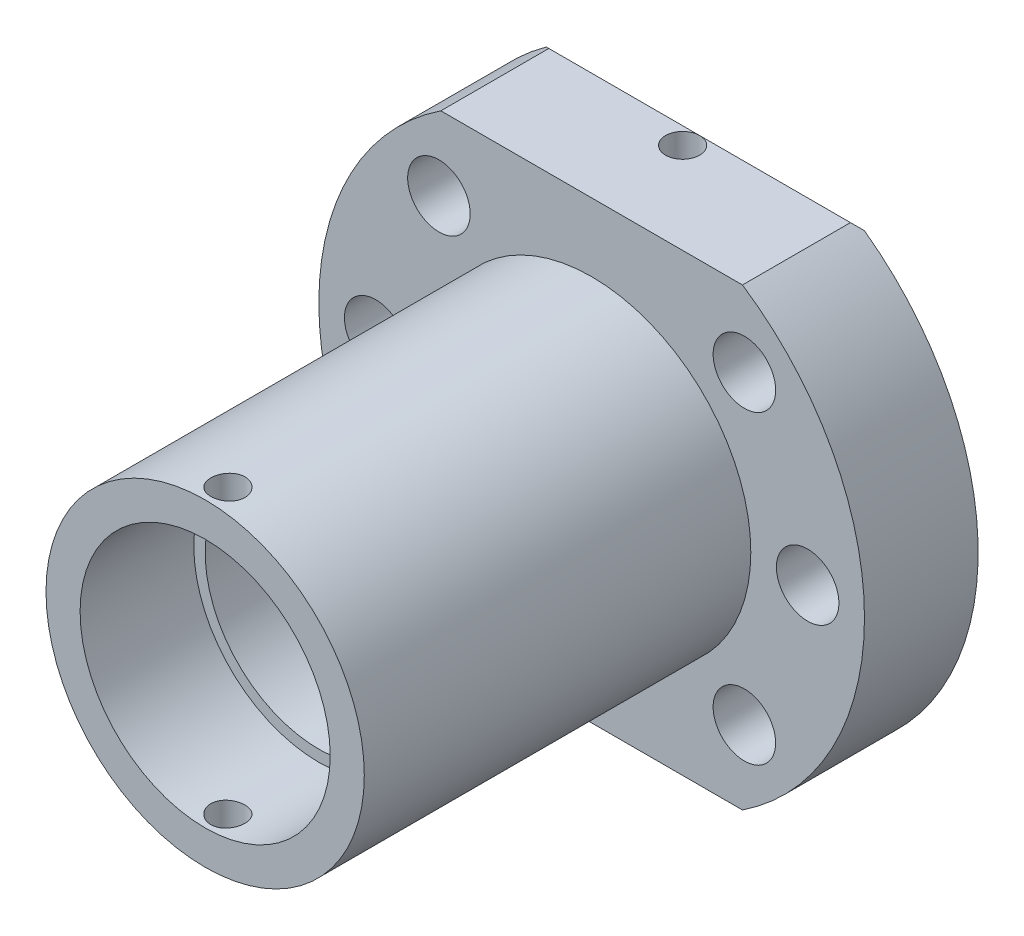
SolidWorks part; units mm, degrees
note: The reader was unsure of these and kept them because the rebuilt part matched: shared geometry of "Sketch1<3>".
ref_plane "Front Plane" through (0, 0, 0) normal (0, 0, 1) x (1, 0, 0)
ref_plane "Top Plane" through (0, 0, 0) normal (0, 1, 0) x (1, 0, 0)
ref_plane "Right Plane" through (0, 0, 0) normal (1, 0, 0) x (0, 0, -1)
sketch "Sketch1" plane through (0, 0, 0) normal (0, 0, 1) x (1, 0, 0)
  line L0 (0, 29.6092) -> (0, -29.6092) construction
  line L1 (-13.2665, 20) -> (13.2665, 20)
  line L2 (-28.8526, 0) -> (28.8526, 0) construction
  line L3 (-13.2665, -20) -> (13.2665, -20)
  circle A0 centre (0, 0) radius 11
  circle A1 centre (0, 0) radius 14
  circle A2 centre (0, 0) radius 19 construction
  arc A3 (-13.2665, 20) -> (-13.2665, -20) centre (0, 0) ccw
  circle A4 centre (19, 0) radius 2.75
  circle A5 centre (13.435, -13.435) radius 2.75
  circle A7 centre (0, -19) radius 2.75 [skipped]
  circle A8 centre (13.435, 13.435) radius 2.75
  circle A9 centre (-13.435, -13.435) radius 2.75
  circle A10 centre (-19, 0) radius 2.75
  circle A11 centre (-13.435, 13.435) radius 2.75
  arc A12 (13.2665, -20) -> (13.2665, 20) centre (0, 0) ccw
  circle A13 centre (0, 0) radius 10
  point P10 (0, 0)
  point P15 (0, 0)
  point P25 (0, 0)
  dimension "D1" = 38
  dimension "D2" = 48
  dimension "D4" = 22
  dimension "D5" = 28
  dimension "D6" = 5.5
  dimension "D9" = 20
  dimension "D3" = 40
  dimension "D8" = 26.8701
  dimension "D7" = 3
extrude "Boss-Extrude1" add sketch "Sketch1" against normal blind 10 contours L3 A12 L1 A3 A10 A8 A5 A4 A1 A9 A11
extrude "Boss-Extrude2" add sketch "Sketch1<3>" along normal blind 24 separate body contours A1 A0 | A0 A13
sketch "Sketch1<3>" plane through (0, 0, 0) normal (0, 0, 1) x (1, 0, 0) same geometry as "Sketch1"
sketch "Sketch3" plane through (0, 0, 24) normal (0, 0, 1) x (1, 0, 0)
  circle A0 centre (0, 0) radius 14
  circle A1 centre (0, 0) radius 11
  point P5 (0, 0)
  dimension "D1" = 28
  dimension "D2" = 22
extrude "Boss-Extrude3" add sketch "Sketch3" along normal blind 10
chamfer "Chamfer1" distance 0.5 angle 45 2 edges at (0, -20, -10) (0, 20, -10)
sketch "Sketch4" plane through (0, 20, 0) normal (0, 1, 0) x (1, 0, 0)
  line L0 (-13.9911, 10) -> (13.9911, 10) construction
  line L1 (13.2665, 9.5) -> (-13.2665, 9.5) construction
  circle A0 centre (0, 8) radius 1.5
  circle A1 centre (0, -32) radius 1.5
  point P4 (0, 0)
  point P6 (0, 0)
  point P7 (0, 7.3571)
  point P10 (0, 0)
  dimension "D1" = 40
  dimension "D2" = 2
extrude "Cut-Extrude1" cut sketch "Sketch4" against normal through all
ref_plane "Plane1" through (0, 0, -5) normal (0, 0, 1) x (1, 0, 0)
sketch "Sketch7" plane through (0, 0, -5) normal (0, 0, 1) x (1, 0, 0)
  line L0 (0, 0) -> (-27.5701, 11.4199) construction
  line L1 (0, 0) -> (-29.5748, 0) construction
  line L3 (-11.5784, 8.0431) -> (-11.7697, 7.5812)
  line L4 (-11.7697, 7.5812) -> (-7.6897, 5.8912)
  line L5 (-7.6897, 5.8912) -> (-8.6464, 3.5815)
  line L12 (-21.9177, 13.4082) -> (-10.2718, 8.5843) construction
  line L13 (-10.2718, 8.5843) -> (-10.4631, 8.1224) construction
  line L14 (-10.4631, 8.1224) -> (-6.3832, 6.4324) construction
  line L15 (-23.7378, 9.8325) -> (-8.6464, 3.5815)
  line L16 (-6.3832, 6.4324) -> (-8.1052, 2.2749) construction
  line L17 (-24.1025, 8.9012) -> (-8.1052, 2.2749) construction
  line L18 (-22.814, 9.4498) -> (-8.6464, 3.5815) construction
  line L19 (-11.5784, 8.0431) -> (-22.4274, 12.5369)
  line L20 (-21.4969, 12.1515) -> (-11.5784, 8.0431) construction
  arc A2 (-22.4274, 12.5369) -> (-23.7378, 9.8325) centre (0, 0) ccw
  arc A3 (-21.4969, 12.1515) -> (-22.814, 9.4498) centre (0, 0) ccw construction
  arc A4 (-21.9177, 13.4082) -> (-24.1025, 8.9012) centre (0, 0) ccw construction
  dimension "D1" = 22.5
  dimension "D2" = 3
  dimension "D3" = 5
  dimension "D5" = 14
  dimension "D4" = 1
revolve "Cut-Revolve3" cut sketch "Sketch7" angle 360 about L15
